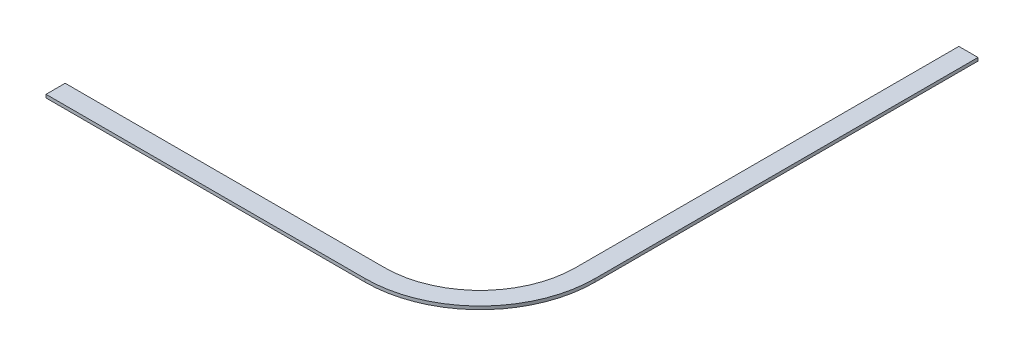
SolidWorks part; units mm, degrees
ref_plane "Front Plane" through (0, 0, 0) normal (0, 0, 1) x (1, 0, 0)
ref_plane "Top Plane" through (0, 0, 0) normal (0, 1, 0) x (1, 0, 0)
ref_plane "Right Plane" through (0, 0, 0) normal (1, 0, 0) x (0, 0, -1)
sketch "Sketch1" plane through (0, 0, 0) normal (0, 1, 0) x (1, 0, 0)
  line L0 (0, 400) -> (0, -200)
  line L1 (-150, -350) -> (-650, -350)
  line L4 (30, -200) -> (30, 400)
  line L5 (30, 400) -> (0, 400)
  line L6 (-650, -380) -> (-150, -380)
  line L7 (-650, -350) -> (-650, -380)
  arc A0 (0, -200) -> (-150, -350) centre (-150, -200) cw
  arc A2 (30, -200) -> (-150, -380) centre (-150, -200) cw
  point P2 (-650, -380)
  point P8 (0, 0)
  dimension "D2" = 150
  dimension "D3" = 180
  dimension "D1" = 30
  dimension "D4" = 400
  dimension "D5" = 30
  dimension "D6" = 500
  dimension "D7" = 90
  dimension "D8" = 600
extrude "Boss-Extrude1" add sketch "Sketch1" along normal blind 5
